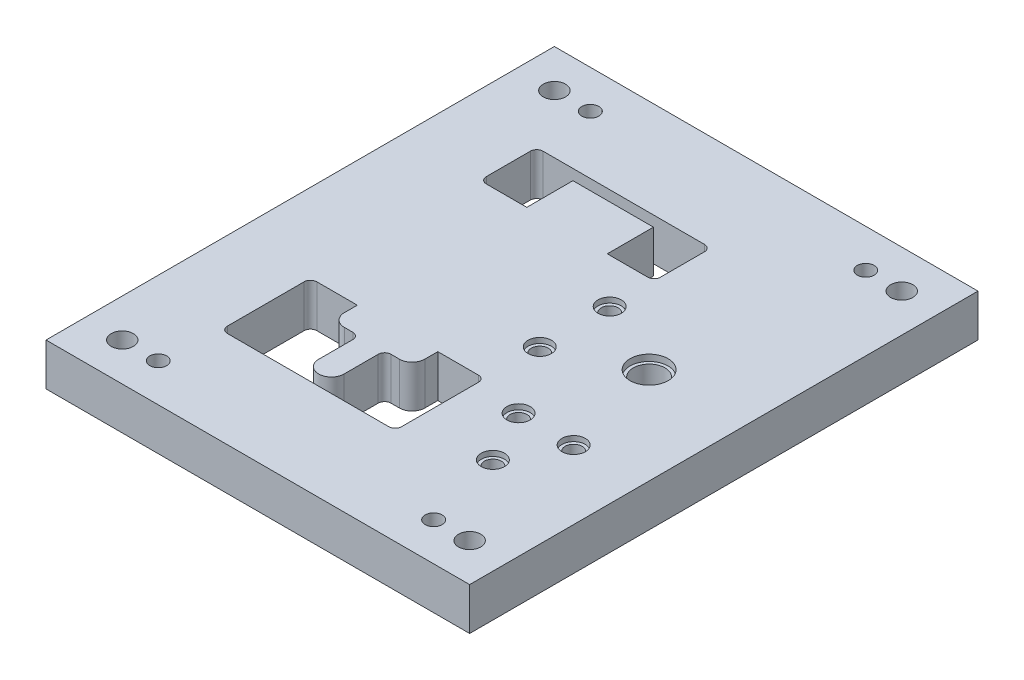
SolidWorks part; units mm, degrees
material "Plain Carbon Steel"
ref_plane "Front Plane" through (0, 0, 0) normal (0, 0, 1) x (1, 0, 0)
ref_plane "Top Plane" through (0, 0, 0) normal (0, 1, 0) x (1, 0, 0)
ref_plane "Right Plane" through (0, 0, 0) normal (1, 0, 0) x (0, 0, -1)
sketch "Sketch1" plane through (0, 0, 0) normal (0, 1, 0) x (1, 0, 0)
  line L1 (-100, -120) -> (100, -120)
  line L2 (-100, -120) -> (-100, 120)
  line L3 (-100, 120) -> (100, 120)
  line L4 (100, -120) -> (100, 120)
  line L5 (-100, -120) -> (100, 120) construction
  line L6 (-100, 120) -> (100, -120) construction
  point P0 (0, 0)
  dimension "D1" = 240
  dimension "D2" = 200
extrude "Boss-Extrude1" add sketch "Sketch1" against normal blind 20
sketch "Sketch5" plane through (0, 0, 0) normal (0, 1, 0) x (1, 0, 0)
  line L1 (8.38, -74.53) -> (-62.87, -74.53) construction
  line L2 (-62.87, -32.27) -> (-62.87, -74.53) construction
  line L3 (-62.87, -32.27) -> (-40.75, -32.27) construction
  line L4 (-40.75, -32.27) -> (-40.75, -38.4) construction
  line L5 (-34.75, -44.4) -> (-30.75, -44.4) construction
  line L6 (-27.75, -47.4) -> (-27.75, -63.53) construction
  line L7 (-15.75, -63.53) -> (-15.75, -47.4) construction
  line L8 (-12.75, -44.4) -> (-8.75, -44.4) construction
  line L9 (-2.75, -38.4) -> (-2.75, -32.27) construction
  line L10 (-2.75, -32.27) -> (8.38, -32.27) construction
  line L11 (-62.87, -35.27) -> (-62.87, -71.53)
  line L12 (16.37, -74.53) -> (-59.87, -74.53)
  line L14 (-2.75, -32.27) -> (16.37, -32.27)
  line L15 (-2.75, -38.4) -> (-2.75, -32.27)
  line L16 (-12.75, -44.4) -> (-8.75, -44.4)
  line L17 (-15.75, -63.53) -> (-15.75, -47.4)
  line L18 (-27.75, -47.4) -> (-27.75, -63.53)
  line L19 (-34.75, -44.4) -> (-30.75, -44.4)
  line L20 (-40.75, -32.27) -> (-40.75, -38.4)
  line L21 (-59.87, -32.27) -> (-40.75, -32.27)
  line L23 (-21.75, -63.53) -> (-21.75, -74.53) construction
  line L25 (19.37, -35.27) -> (19.37, -71.53)
  arc A0 (-40.75, -38.4) -> (-34.75, -44.4) centre (-34.75, -38.4) ccw construction
  arc A1 (-27.75, -47.4) -> (-30.75, -44.4) centre (-30.75, -47.4) ccw construction
  arc A2 (-27.75, -63.53) -> (-15.75, -63.53) centre (-21.75, -63.53) ccw construction
  arc A3 (-12.75, -44.4) -> (-15.75, -47.4) centre (-12.75, -47.4) ccw construction
  arc A4 (-8.75, -44.4) -> (-2.75, -38.4) centre (-8.75, -38.4) ccw construction
  arc A5 (-8.75, -44.4) -> (-2.75, -38.4) centre (-8.75, -38.4) ccw
  arc A6 (-12.75, -44.4) -> (-15.75, -47.4) centre (-12.75, -47.4) ccw
  arc A7 (-27.75, -63.53) -> (-15.75, -63.53) centre (-21.75, -63.53) ccw
  arc A8 (-27.75, -47.4) -> (-30.75, -44.4) centre (-30.75, -47.4) ccw
  arc A9 (-40.75, -38.4) -> (-34.75, -44.4) centre (-34.75, -38.4) ccw
  arc A10 (19.37, -71.53) -> (16.37, -74.53) centre (16.37, -71.53) cw
  arc A11 (19.37, -35.27) -> (16.37, -32.27) centre (16.37, -35.27) ccw
  arc A12 (-62.87, -35.27) -> (-59.87, -32.27) centre (-59.87, -35.27) cw
  arc A13 (-62.87, -71.53) -> (-59.87, -74.53) centre (-59.87, -71.53) ccw
  dimension "D1" = 3
extrude "Cut-Extrude3" cut sketch "Sketch5" against normal up to next
sketch "Sketch6" plane through (0, 0, 0) normal (0, 1, 0) x (1, 0, 0)
  line L0 (-62.87, 47.73) -> (-62.87, 74.53) construction
  line L1 (-40.75, 47.73) -> (-62.87, 47.73) construction
  line L2 (-40.75, 69.53) -> (-40.75, 47.73) construction
  line L3 (-2.75, 69.53) -> (-40.75, 69.53) construction
  line L4 (-2.75, 47.73) -> (-2.75, 69.53) construction
  line L5 (8.38, 47.73) -> (-2.75, 47.73) construction
  line L7 (-62.87, 74.53) -> (8.38, 74.53) construction
  line L8 (-62.87, 50.73) -> (-62.87, 71.53)
  line L9 (-40.75, 47.73) -> (-59.87, 47.73)
  line L10 (-40.75, 69.53) -> (-40.75, 47.73)
  line L11 (-2.75, 69.53) -> (-40.75, 69.53)
  line L12 (-2.75, 47.73) -> (-2.75, 69.53)
  line L13 (16.37, 47.73) -> (-2.75, 47.73)
  line L15 (-59.87, 74.53) -> (16.37, 74.53)
  line L16 (-21.75, 69.53) -> (-21.75, 47.73) construction
  line L17 (19.37, 71.53) -> (19.37, 50.73)
  arc A0 (19.37, 71.53) -> (16.37, 74.53) centre (16.37, 71.53) ccw
  arc A1 (19.37, 50.73) -> (16.37, 47.73) centre (16.37, 50.73) cw
  arc A2 (-62.87, 50.73) -> (-59.87, 47.73) centre (-59.87, 50.73) ccw
  arc A3 (-62.87, 71.53) -> (-59.87, 74.53) centre (-59.87, 71.53) cw
  dimension "D1" = 3
extrude "Cut-Extrude4" cut sketch "Sketch6" against normal up to next
sketch "Sketch7" plane through (0, 0, 0) normal (0, 1, 0) x (1, 0, 0)
  circle A3 centre (54.5, -63.53) radius 4
  circle A4 centre (67.5, -38.4) radius 4
  circle A5 centre (41.5, -38.4) radius 4
  circle A6 centre (19.38, -6.27) radius 4
  circle A7 centre (19.38, 26.73) radius 4
  dimension "D1" = 8
extrude "Cut-Extrude5" cut sketch "Sketch7" against normal up to next
sketch "Sketch9" plane through (0, 0, 0) normal (0, 1, 0) x (1, 0, 0)
  circle A0 centre (54.5, 10.23) radius 7.5
  dimension "D1" = 15
extrude "Cut-Extrude6" cut sketch "Sketch9" against normal up to next
sketch "Sketch10" plane through (0, 0, 0) normal (0, 1, 0) x (1, 0, 0)
  circle A0 centre (19.38, 26.73) radius 5.5
  circle A1 centre (19.38, -6.27) radius 5.5
  circle A2 centre (41.5, -38.4) radius 5.5
  circle A3 centre (67.5, -38.4) radius 5.5
  circle A4 centre (54.5, -63.53) radius 5.5
  dimension "D1" = 11
extrude "Cut-Extrude7" cut sketch "Sketch10" against normal blind 2.5
sketch "Sketch11" plane through (0, 0, 0) normal (0, 1, 0) x (1, 0, 0)
  circle A0 centre (54.5, 10.23) radius 9
  dimension "D1" = 18
extrude "Cut-Extrude8" cut sketch "Sketch11" against normal blind 3
sketch "Sketch12" plane through (0, 0, 0) normal (0, 1, 0) x (1, 0, 0)
  circle A0 centre (19.38, 26.73) radius 2.5
  circle A1 centre (19.38, -6.27) radius 2.5
  circle A2 centre (41.5, -38.4) radius 2.5
  circle A3 centre (67.5, -38.4) radius 2.5
  circle A4 centre (54.5, -63.53) radius 2.5
  dimension "D1" = 5
hole_wizard "CBORE for M10 Hex Socket Head Cap Screw1" positions "Sketch18" profile "Sketch16" counterbore size "M10" standard "ISO" end condition through all
sketch "Sketch18" plane through (0, -20, 0) normal (0, -1, 0) x (-1, 0, 0)
  line L0 (-100, 120) -> (100, 120) construction
  line L1 (-100, -120) -> (-100, 120) construction
  line L2 (100, 120) -> (100, -120) construction
  line L3 (100, -120) -> (-100, -120) construction
  point P0 (-82, 102)
  point P2 (82, 102)
  point P4 (82, -102)
  point P6 (-82, -102)
  point P13 (0, 0)
  point P18 (0, 0)
  point P19 (0, 0)
  point P20 (0, 0)
  point P21 (0, 0)
  dimension "D1" = 18
  dimension "D2" = 18
  dimension "D3" = 18
  dimension "D4" = 18
sketch "Sketch16" plane through (82, -20, -102) normal (1, 0, 0) x (0, 0, -1)
  line L0 (0, 0) -> (0, 20)
  line L1 (0, 20) -> (5.25, 20)
  line L3 (5.25, 20) -> (5.25, 10.6)
  line L4 (9, 10.6) -> (5.25, 10.6)
  line L5 (9, 10.6) -> (9, 0.025)
  line L6 (9, 0.025) -> (9.025, 0)
  line L7 (9.025, 0) -> (0, 0)
  line L8 (-9, 0.025) -> (-9.025, 0) construction
  line L11 (0, -6.35) -> (0, 107.95) construction
  dimension "Thru Hole Dia." = 10.5
  dimension "Thru Hole Depth" = 20
  dimension "C'Bore Dia." = 18
  dimension "C'Bore Depth" = 10.6
  dimension "Near C'Sink Dia." = 18.05
  dimension "Near C'Sink Angle" = 90
hole_wizard "Ø8.0mm Dowel Hole1" positions "Sketch21" profile "Sketch20" hole size "Ø8.0" standard "ISO" end condition through all
sketch "Sketch21" plane through (0, -20, 0) normal (0, -1, 0) x (-1, 0, 0)
  line L0 (-100, 120) -> (100, 120) construction
  line L1 (100, -120) -> (-100, -120) construction
  circle A0 centre (-82, 102) radius 9.025 construction
  circle A1 centre (82, 102) radius 9.025 construction
  point P0 (-65, 102)
  point P2 (65, 102)
  point P4 (65, -102)
  point P6 (-65, -102)
  point P17 (0, 0)
  point P18 (0, 0)
  point P19 (0, 0)
  point P20 (0, 0)
  dimension "D2" = 17
  dimension "D1" = 17
  dimension "D3" = 18
  dimension "D4" = 18
sketch "Sketch20" plane through (65, -20, -102) normal (1, 0, 0) x (0, 0, -1)
  line L0 (0, 0) -> (0, 20)
  line L1 (0, 20) -> (4, 20)
  line L2 (4, 20) -> (4, 0)
  line L5 (4, 0) -> (0, 0)
  line L11 (0, -6.35) -> (0, 107.95) construction
  dimension "Thru Hole Dia." = 8
  dimension "Thru Hole Depth" = 20
